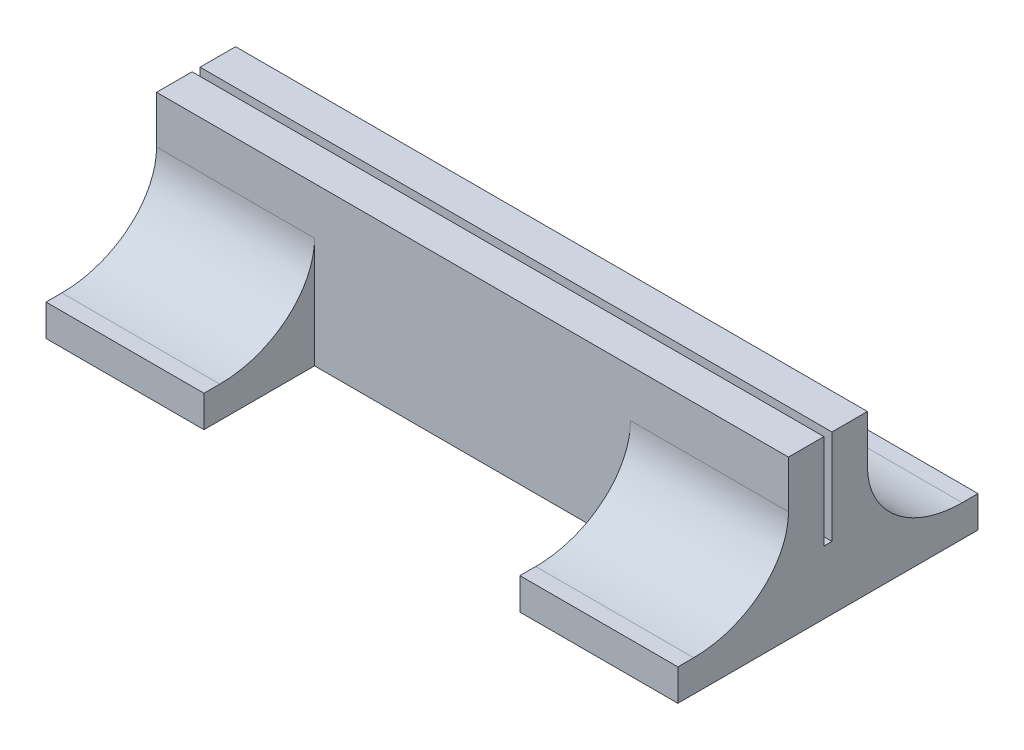
SolidWorks part; units mm, degrees
ref_plane "Front Plane" through (0, 0, 0) normal (0, 0, 1) x (1, 0, 0)
ref_plane "Top Plane" through (0, 0, 0) normal (0, 1, 0) x (1, 0, 0)
ref_plane "Right Plane" through (0, 0, 0) normal (1, 0, 0) x (0, 0, -1)
sketch "Esquisse1" plane through (0, 0, 0) normal (0, 1, 0) x (1, 0, 0)
  line L1 (-20, 2.5) -> (20, 2.5)
  line L2 (-20, 2.5) -> (-20, -2.5)
  line L3 (-20, -2.5) -> (20, -2.5)
  line L4 (20, 2.5) -> (20, -2.5)
  line L5 (-20, 2.5) -> (20, -2.5) construction
  line L6 (-20, -2.5) -> (20, 2.5) construction
  point P0 (0, 0)
extrude "Boss.-Extru.1" add sketch "Esquisse1" along normal blind 10
sketch "Esquisse2" plane through (0, 10, 0) normal (0, 1, 0) x (1, 0, 0)
  line L0 (-20, 2.5) -> (-20, -2.5) construction
  line L1 (20, -0.2542) -> (-20, -0.2542)
  line L2 (20, -0.2542) -> (20, 0.2542)
  line L3 (20, 0.2542) -> (-20, 0.2542)
  line L4 (-20, -0.2542) -> (-20, 0.2542)
  line L5 (20, -0.2542) -> (-20, 0.2542) construction
  line L6 (20, 0.2542) -> (-20, -0.2542) construction
  point P0 (0, 0)
extrude "Enlèv. mat.-Extru.1" cut sketch "Esquisse2" against normal blind 6
sketch "Esquisse3" plane through (0, 0, 2.5) normal (0, 0, 1) x (1, 0, 0)
  line L1 (-20, 0) -> (-10, 0)
  line L2 (-20, 0) -> (-20, 2)
  line L3 (-20, 2) -> (-10, 2)
  line L4 (-10, 0) -> (-10, 2)
extrude "Boss.-Extru.2" add sketch "Esquisse3" along normal blind 7 and the other way blind 12
mirror "Symétrie1" about plane through (0, 0, 0) normal (1, 0, 0) of "Boss.-Extru.2"
fillet "Congé1" radius 6 1 edges at (-15, 2, 2.5) second distance 5 first distance on face at (-15, 2, 6)
fillet "Congé2" radius 5 1 edges at (15, 2, 2.5) second distance 6 first distance on face at (-0.625, 5.375, 2.5)
fillet "Congé4" radius 5 1 edges at (15, 2, -2.5) second distance 6 first distance on face at (0, 3.5, -2.5)
fillet "Congé5" radius 6 1 edges at (-15, 2, -2.5) second distance 5 first distance on face at (-15, 2, -6)
